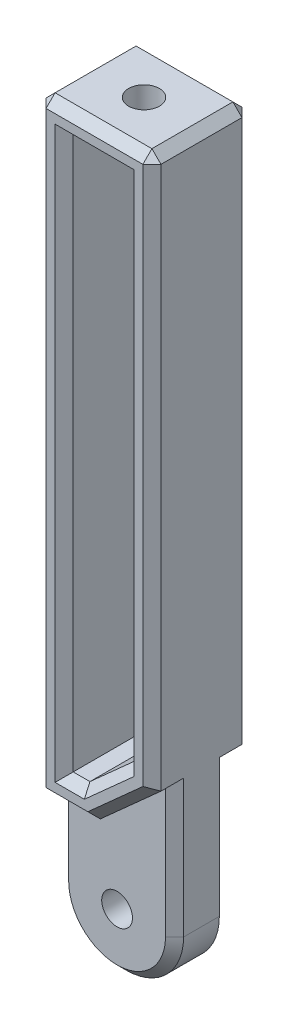
SolidWorks part; units mm, degrees
ref_plane "Front Plane" through (0, 0, 0) normal (0, 0, 1) x (1, 0, 0)
ref_plane "Top Plane" through (0, 0, 0) normal (0, 1, 0) x (1, 0, 0)
ref_plane "Right Plane" through (0, 0, 0) normal (1, 0, 0) x (0, 0, -1)
sketch "Sketch1" plane through (0, 0, 0) normal (0, 0, 1) x (1, 0, 0)
  line L2 (-6.35, 0) -> (-6.35, 76.2)
  line L3 (-6.35, 76.2) -> (6.35, 76.2)
  line L4 (6.35, 0) -> (6.35, 76.2)
  arc A1 (-6.35, 0) -> (6.35, 0) centre (0, 0) ccw
  point P5 (0, 0)
  point P7 (0, 0)
  dimension "D2" = 6.35
  dimension "D1" = 76.2
extrude "Boss-Extrude1" add sketch "Sketch1" along normal mid plane 5.95
sketch "Sketch4" plane through (0, 0, 2.975) normal (0, 0, 1) x (1, 0, 0)
  line L0 (-6.35, 76.2) -> (-6.35, 9.2)
  line L1 (-6.35, 76.2) -> (-6.35, 0) construction
  line L2 (-6.35, 9.2) -> (-0.35, 9.2)
  line L3 (-0.35, 9.2) -> (6.35, 15.2092)
  line L4 (6.35, 0) -> (6.35, 76.2) construction
  line L5 (6.35, 15.2092) -> (6.35, 76.2)
  line L6 (6.35, 76.2) -> (-6.35, 76.2)
  dimension "D1" = 6
  dimension "D2" = 67
  dimension "D3" = 9
extrude "Boss-Extrude2" add sketch "Sketch4" along normal blind 2.5
extrude "Boss-Extrude3" add sketch "Sketch4<2>" against normal blind 2.5 from surface starting at face at (0, 36.5125, -2.975)
sketch "Sketch4<2>" plane through (0, 0, 2.975) normal (0, 0, 1) x (1, 0, 0) same geometry as "Sketch4"
sketch "Sketch5" plane through (0, 0, 5.475) normal (0, 0, 1) x (1, 0, 0)
  line L10 (3.35, 73.2) -> (-3.35, 73.2)
  line L11 (-3.35, 73.2) -> (-3.35, 12.2)
  line L12 (-3.35, 12.2) -> (-1.4982, 12.2)
  line L13 (-1.4982, 12.2) -> (3.35, 16.5483)
  line L14 (3.35, 16.5483) -> (3.35, 73.2)
  line L15 (3.35, 73.2) -> (-3.35, 73.2)
  line L16 (-3.35, 73.2) -> (-3.35, 12.2)
  line L17 (-3.35, 12.2) -> (-1.4982, 12.2)
  line L18 (-1.4982, 12.2) -> (3.35, 16.5483)
  line L19 (3.35, 16.5483) -> (3.35, 73.2)
  dimension "D1" = 3
extrude "Cut-Extrude3" cut sketch "Sketch5" against normal through all
sketch "Sketch6" plane through (0, 73.2, 0) normal (0, -1, 0) x (1, 0, 0)
  line L0 (6.35, -5.475) -> (-6.35, -5.475) construction
  line L1 (-6.35, 5.475) -> (-6.35, -5.475) construction
  circle A0 centre (0, 0) radius 1.7
  point P4 (0, -5.475)
  point P7 (-6.35, 0)
  dimension "D1" = 3.4
extrude "Cut-Extrude4" cut sketch "Sketch6" against normal through all
sketch "Sketch7" plane through (0, 0, 2.975) normal (0, 0, 1) x (1, 0, 0)
  circle A0 centre (0, 0) radius 1.7
  arc A1 (-6.35, 0) -> (6.35, 0) centre (0, 0) ccw construction
  dimension "D1" = 3.4
extrude "Cut-Extrude5" cut sketch "Sketch7" against normal through all
chamfer "Chamfer1" distance 1 angle 45 28 edges at (6.35, 45.7046, -5.475) (0, 76.2, -5.475) (-6.35, 42.7, -5.475) (-3.35, 9.2, -5.475) (3, 12.2046, -5.475) (-2.4241, 12.2, -5.475) (-3.35, 42.7, -5.475) (0, 73.2, -5.475) (3.35, 44.8742, -5.475) (0.9259, 14.3742, -5.475) (0, 76.2, 5.475) (6.35, 45.7046, 5.475) (3, 12.2046, 5.475) (-3.35, 9.2, 5.475) (-6.35, 42.7, 5.475) (-2.4241, 12.2, 5.475) (0.9259, 14.3742, 5.475) (3.35, 44.8742, 5.475) (0, 73.2, 5.475) (-3.35, 42.7, 5.475) (-6.35, 4.6, -2.975) (0, -6.35, -2.975) (6.35, 7.6046, -2.975) (-6.35, 4.6, 2.975) (0, -6.35, 2.975) (6.35, 7.6046, 2.975) (-6.35, 76.2, 0) (6.35, 76.2, 0)
